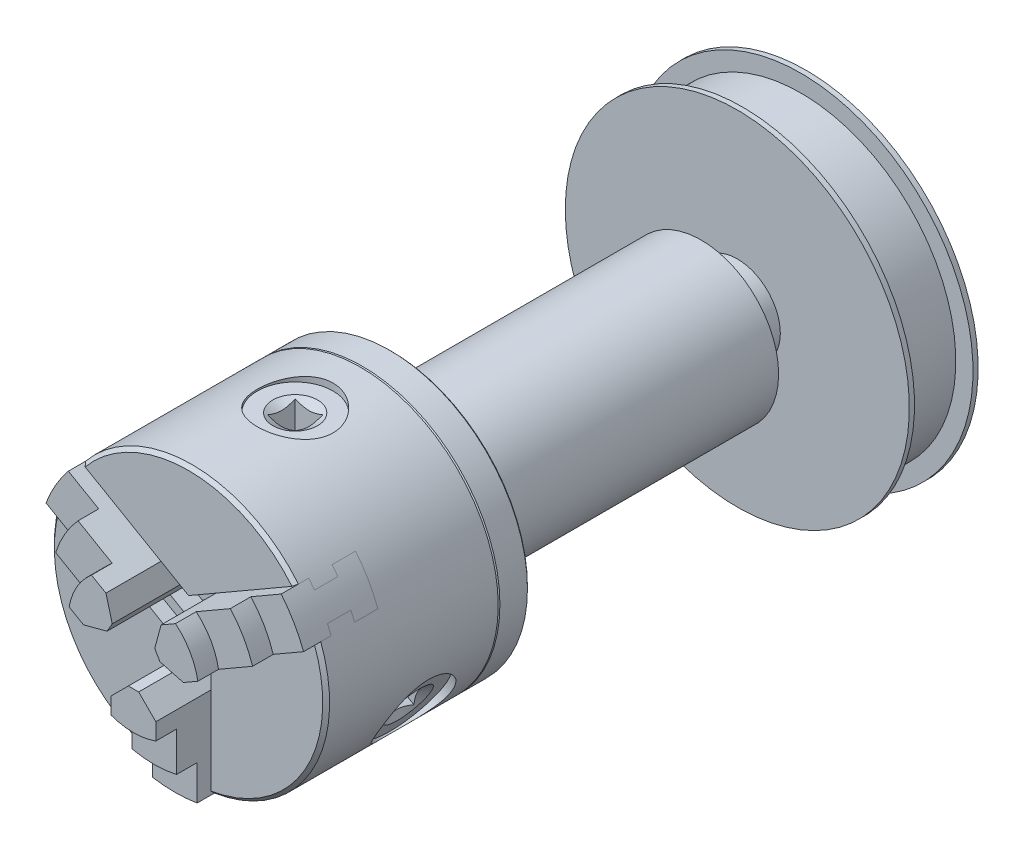
SolidWorks part; units mm, degrees
ref_plane "Front Plane" through (0, 0, 0) normal (0, 0, 1) x (1, 0, 0)
ref_plane "Top Plane" through (0, 0, 0) normal (0, 1, 0) x (1, 0, 0)
ref_plane "Right Plane" through (0, 0, 0) normal (1, 0, 0) x (0, 0, -1)
sketch "Sketch1" plane through (0, 0, 0) normal (0, 0, 1) x (1, 0, 0)
  circle A0 centre (0, 0) radius 22.5
  dimension "D1" = 45
extrude "Boss-Extrude1" add sketch "Sketch1" along normal blind 80
sketch "Sketch2" plane through (0, 0, 0) normal (0, 0, -1) x (-1, 0, 0)
  circle A0 centre (0, 0) radius 12.5
  dimension "D1" = 25
extrude "Boss-Extrude2" add sketch "Sketch2" along normal blind 10.5
sketch "Sketch3" plane through (0, 0, -10.5) normal (0, 0, -1) x (-1, 0, 0)
  circle A0 centre (0, 0) radius 50
  dimension "D1" = 100
extrude "Boss-Extrude3" add sketch "Sketch3" along normal blind 1.5
sketch "Sketch4" plane through (0, 0, -12) normal (0, 0, -1) x (-1, 0, 0)
  circle A0 centre (0, 0) radius 45
  dimension "D1" = 90
extrude "Boss-Extrude4" add sketch "Sketch4" along normal blind 17
sketch "Sketch5" plane through (0, 0, -29) normal (0, 0, -1) x (-1, 0, 0)
  circle A0 centre (0, 0) radius 50
extrude "Boss-Extrude5" add sketch "Sketch5" along normal blind 1.5
sketch "Sketch6" plane through (0, 0, -30.5) normal (0, 0, -1) x (-1, 0, 0)
  circle A0 centre (0, 0) radius 12.5
extrude "Boss-Extrude6" add sketch "Sketch6" along normal blind 1.5 separate body
sketch "Sketch7" plane through (0, 0, -32) normal (0, 0, -1) x (-1, 0, 0)
  circle A0 centre (0, 0) radius 6
extrude "Boss-Extrude7" add sketch "Sketch7" along normal blind 8 separate body
sketch "Sketch8" plane through (0, 0, 80) normal (0, 0, 1) x (1, 0, 0)
  circle A0 centre (0, 0) radius 12.5
extrude "Boss-Extrude8" add sketch "Sketch8" along normal blind 2
sketch "Sketch9" plane through (0, 0, 82) normal (0, 0, 1) x (1, 0, 0)
  circle A0 centre (0, 0) radius 22.5
extrude "Boss-Extrude9" add sketch "Sketch9" along normal blind 8
sketch "Sketch10" plane through (0, 0, 90) normal (0, 0, 1) x (1, 0, 0)
  circle A0 centre (0, 0) radius 40
extrude "Boss-Extrude10" add sketch "Sketch10" along normal blind 9
chamfer "Chamfer1" distance 0.5 angle 45 2 edges at (40, 0, 99) (40, 0, 90)
sketch "Sketch11" plane through (0, 0, 99) normal (0, 0, 1) x (1, 0, 0)
  circle A0 centre (0, 0) radius 40
  dimension "D1" = 80
extrude "Boss-Extrude11" add sketch "Sketch11" along normal blind 50
chamfer "Chamfer2" distance 1 angle 45 1 edges at (40, 0, 149)
sketch "Sketch12" plane through (0, 0, 0) normal (0, 1, 0) x (1, 0, 0)
  line L0 (-39, -149) -> (39, -149) construction
  line L1 (0, 0) -> (0, -162.2804) construction
  circle A0 centre (0, -118) radius 11
  dimension "D1" = 22
  dimension "D2" = 31
extrude "Cut-Extrude1" cut sketch "Sketch12" along normal through all from offset 38
sketch "Sketch13" plane through (0, 38, 0) normal (0, 1, 0) x (1, 0, 0)
  line L1 (-4, -122) -> (4, -122)
  line L2 (-4, -122) -> (-4, -114)
  line L3 (-4, -114) -> (4, -114)
  line L4 (4, -122) -> (4, -114)
  line L5 (-4, -122) -> (4, -114) construction
  line L6 (-4, -114) -> (4, -122) construction
  point P0 (0, -118)
  dimension "D1" = 8
  dimension "D2" = 8
extrude "Cut-Extrude2" cut sketch "Sketch13" against normal blind 13
sketch "Sketch14" plane through (0, 38, 0) normal (0, 1, 0) x (1, 0, 0)
  circle A0 centre (0, -118) radius 6.5
extrude "Cut-Extrude3" cut sketch "Sketch14" against normal through all draft 60
pattern_circular "CirPattern1" count 3 over 360 about axis through (0, 0, 149) along (0, 0, 1) of "Cut-Extrude1", "Cut-Extrude2", "Cut-Extrude3"
sketch "Sketch16" plane through (0, 0, 0) normal (0, 1, 0) x (1, 0, 0)
  line L0 (-39, -149) -> (39, -149) construction
  line L1 (-6.5, -153) -> (-3.7675, -153)
  line L2 (-6.5, -153) -> (-6.5, -145)
  line L3 (-6.5, -145) -> (-3.7675, -145)
  line L4 (6.5, -153) -> (6.5, -145)
  line L5 (3.7675, -138.2) -> (6.5, -138.2)
  line L6 (3.7675, -145) -> (3.7675, -138.2)
  line L7 (3.7675, -153) -> (6.5, -153)
  line L8 (-3.7675, -155.2) -> (3.7675, -155.2)
  line L9 (-3.7675, -155.2) -> (-3.7675, -153)
  line L11 (3.7675, -155.2) -> (3.7675, -153)
  line L14 (-6.5, -138.2) -> (-3.7675, -138.2)
  line L15 (-6.5, -138.2) -> (-6.5, -131.4)
  line L16 (-6.5, -131.4) -> (6.5, -131.4)
  line L17 (6.5, -138.2) -> (6.5, -131.4)
  line L20 (-3.7675, -145) -> (-3.7675, -138.2)
  line L21 (3.7675, -145) -> (6.5, -145)
  point P0 (0, -149)
  point P7 (0, -145)
  dimension "D1" = 13
  dimension "D2" = 13
  dimension "D3" = 6.8
  dimension "D4" = 6.8
  dimension "D5" = 4
extrude "Cut-Extrude4" cut sketch "Sketch16" against normal through all
pattern_circular "CirPattern2" count 3 over 360 about axis through (0, 0, 149) along (0, 0, 1) of "Cut-Extrude4"
sketch "Sketch17" plane through (0, 0, 0) normal (0, 1, 0) x (1, 0, 0)
  line L0 (-6.5, -165) -> (6.5, -165)
  line L16 (-6.5, -153) -> (-3.7675, -153)
  line L17 (-6.5, -145) -> (-6.5, -153)
  line L18 (-3.7675, -145) -> (-6.5, -145)
  line L19 (-3.7675, -138.2) -> (-3.7675, -145)
  line L20 (-6.5, -138.2) -> (-3.7675, -138.2)
  line L21 (-6.5, -131.4) -> (-6.5, -138.2)
  line L22 (6.5, -131.4) -> (-6.5, -131.4)
  line L23 (6.5, -138.2) -> (6.5, -131.4)
  line L24 (3.7675, -138.2) -> (6.5, -138.2)
  line L25 (3.7675, -145) -> (3.7675, -138.2)
  line L26 (6.5, -145) -> (3.7675, -145)
  line L27 (6.5, -153) -> (6.5, -145)
  line L28 (3.7675, -153) -> (6.5, -153)
  line L29 (3.7675, -155.2) -> (3.7675, -153)
  line L30 (-3.7675, -155.2) -> (3.7675, -155.2)
  line L31 (-3.7675, -153) -> (-3.7675, -155.2)
  line L33 (-6.5, -145) -> (-6.5, -165)
  line L34 (-3.7675, -145) -> (-6.5, -145)
  line L35 (-3.7675, -138.2) -> (-3.7675, -145)
  line L36 (-6.5, -138.2) -> (-3.7675, -138.2)
  line L37 (-6.5, -131.4) -> (-6.5, -138.2)
  line L38 (6.5, -131.4) -> (-6.5, -131.4)
  line L39 (6.5, -138.2) -> (6.5, -131.4)
  line L40 (3.7675, -138.2) -> (6.5, -138.2)
  line L41 (3.7675, -145) -> (3.7675, -138.2)
  line L42 (6.5, -145) -> (3.7675, -145)
  line L43 (6.5, -165) -> (6.5, -145)
  line L48 (-6.5, -153) -> (-3.7675, -153)
  line L49 (-6.5, -145) -> (-6.5, -153)
  line L50 (-3.7675, -145) -> (-6.5, -145)
  line L51 (-3.7675, -138.2) -> (-3.7675, -145)
  line L52 (-6.5, -138.2) -> (-3.7675, -138.2)
  line L53 (-6.5, -131.4) -> (-6.5, -138.2)
  line L54 (6.5, -131.4) -> (-6.5, -131.4)
  line L55 (6.5, -138.2) -> (6.5, -131.4)
  line L56 (3.7675, -138.2) -> (6.5, -138.2)
  line L57 (3.7675, -145) -> (3.7675, -138.2)
  line L58 (6.5, -145) -> (3.7675, -145)
  line L59 (6.5, -153) -> (6.5, -145)
  line L60 (3.7675, -153) -> (6.5, -153)
  line L61 (3.7675, -155.2) -> (3.7675, -153)
  line L62 (-3.7675, -155.2) -> (3.7675, -155.2)
  line L63 (-3.7675, -153) -> (-3.7675, -155.2)
  line L65 (-6.5, -145) -> (-6.5, -165)
  line L66 (-3.7675, -145) -> (-6.5, -145)
  line L67 (-3.7675, -138.2) -> (-3.7675, -145)
  line L68 (-6.5, -138.2) -> (-3.7675, -138.2)
  line L69 (-6.5, -131.4) -> (-6.5, -138.2)
  line L70 (6.5, -131.4) -> (-6.5, -131.4)
  line L71 (6.5, -138.2) -> (6.5, -131.4)
  line L72 (3.7675, -138.2) -> (6.5, -138.2)
  line L73 (3.7675, -145) -> (3.7675, -138.2)
  line L74 (6.5, -145) -> (3.7675, -145)
  line L75 (6.5, -165) -> (6.5, -145)
  dimension "D3" = 20
  dimension "D1" = 0
  dimension "D2" = 0
extrude "Boss-Extrude12" add sketch "Sketch17" against normal blind 32 from offset 8 separate body contours L0 L43 L42 L41 L40 L39 L38 L37 L36 L35 L34 L33 region at (0, 0, 159.5826) region at (0, 0, 143.0438) offset against normal yes
chamfer "Chamfer3" distance 5 angle 45 2 edges at (-6.5, -8, 155) (6.5, -8, 155)
sketch "Sketch18" plane through (0, 0, 165) normal (0, 0, 1) x (1, 0, 0)
  circle A0 centre (0, 0) radius 19
  circle A1 centre (0, 0) radius 56.9622
  dimension "D1" = 38
sketch "Sketch19" plane through (0, 0, 131.4) normal (0, 0, 1) x (1, 0, 0)
pattern_circular "CirPattern6" count 3 over 360 about axis through (0, 0, 148) along (0, 0, -1) of bodies 118
extrude "Cut-Extrude5" cut sketch "Sketch18" against normal blind 6
sketch "Sketch20" plane through (0, 0, 159) normal (0, 0, 1) x (1, 0, 0)
  circle A0 centre (0, 0) radius 30
  arc A1 (-6.5, -17.8536) -> (6.5, -17.8536) centre (0, 0) ccw construction
  circle A3 centre (0, 0) radius 66.1427
  point P3 (0, -19)
  dimension "D1" = 11
extrude "Cut-Extrude6" cut sketch "Sketch20" against normal blind 6
sketch "Sketch21" plane through (0, 0, 153) normal (0, 0, 1) x (1, 0, 0)
  circle A0 centre (0, 0) radius 40
  circle A1 centre (0, 0) radius 72.1473
extrude "Cut-Extrude7" cut sketch "Sketch21" against normal blind 25
